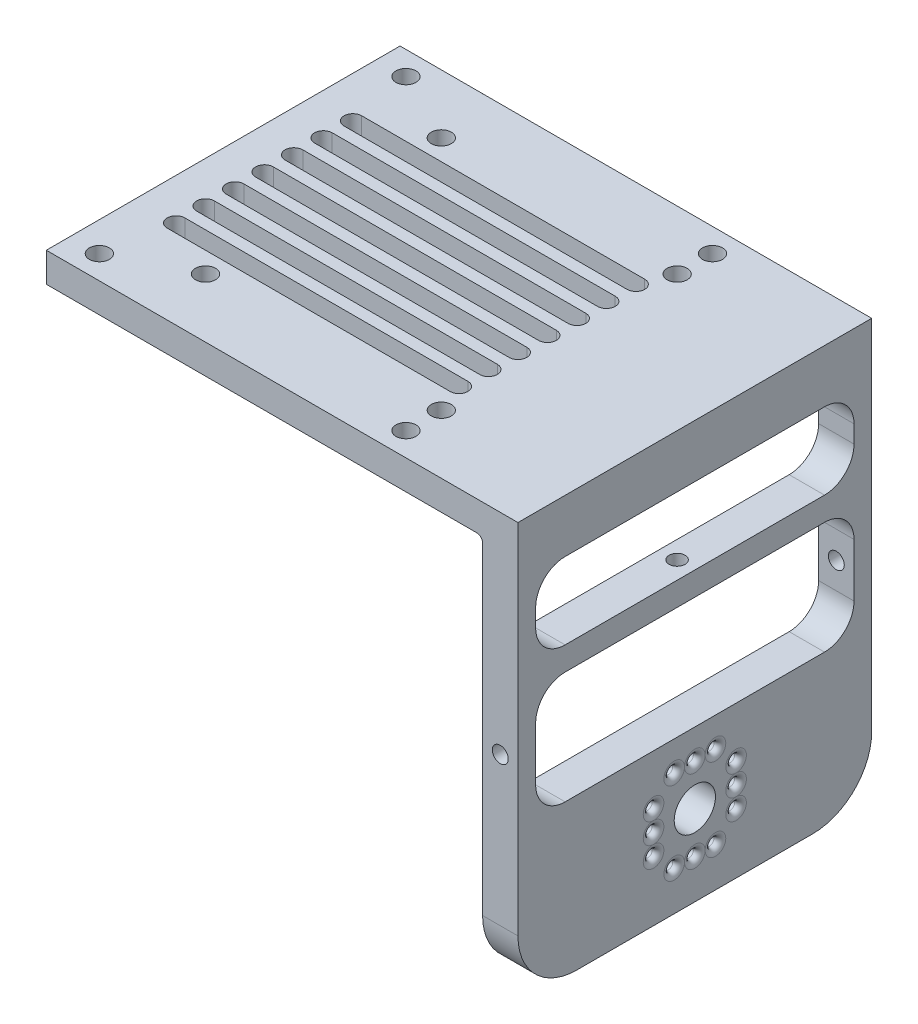
SolidWorks part; units mm, degrees
ref_plane "Front Plane" through (0, 0, 0) normal (0, 0, 1) x (1, 0, 0)
ref_plane "Top Plane" through (0, 0, 0) normal (0, 1, 0) x (1, 0, 0)
ref_plane "Right Plane" through (0, 0, 0) normal (1, 0, 0) x (0, 0, -1)
sketch "Sketch1" plane through (0, 0, 0) normal (0, 1, 0) x (1, 0, 0)
  line L0 (17, 50) -> (17, 10) construction
  line L1 (0, 0) -> (74, 0)
  line L2 (0, 0) -> (0, 60)
  line L3 (0, 60) -> (74, 60)
  line L4 (74, 0) -> (74, 60)
  line L5 (17, 10) -> (57, 10) construction
  line L6 (57, 10) -> (57, 50) construction
  line L7 (57, 50) -> (17, 50) construction
  line L8 (5, -3.2672) -> (5, 68.5158) construction
  line L9 (74, 30) -> (-36.7362, 30) construction
  line L10 (5, 56) -> (78.5335, 56) construction
  line L11 (5, 4) -> (68.1649, 4) construction
  circle A0 centre (17, 50) radius 1.7
  circle A1 centre (57, 50) radius 1.7
  circle A2 centre (57, 10) radius 1.7
  circle A3 centre (17, 10) radius 1.7
  circle A4 centre (5, 4) radius 1.7
  circle A5 centre (5, 56) radius 1.7
  circle A6 centre (57, 56) radius 1.7
  circle A7 centre (57, 4) radius 1.7
  dimension "D5" = 3.4
  dimension "D6" = 3.4
  dimension "D7" = 3.4
  dimension "D8" = 3.4
  dimension "D14" = 3.4
  dimension "D15" = 3.4
  dimension "D16" = 52
  dimension "D17" = 3.4
  dimension "D19" = 3.4
  dimension "D1" = 17
  dimension "D2" = 17
  dimension "D3" = 10
  dimension "D4" = 10
  dimension "D9" = 40
  dimension "D10" = 40
  dimension "D11" = 26
  dimension "D12" = 26
  dimension "D13" = 0
  dimension "D18" = 52
extrude "Boss-Extrude1" add sketch "Sketch1" along normal blind 5
sketch "Sketch2" plane through (0, 5, 0) normal (0, 1, 0) x (1, 0, 0)
  line L0 (0, 0) -> (74, 0) construction
  line L1 (74, 60) -> (80, 60)
  line L2 (74, 60) -> (74, 0)
  line L3 (74, 0) -> (80, 0)
  line L4 (80, 60) -> (80, 0)
  dimension "D1" = 6
  dimension "D2" = 0
extrude "Boss-Extrude2" add sketch "Sketch2" against normal blind 100
sketch "Sketch6" plane through (74, 0, 0) normal (-1, 0, 0) x (0, 0, 1)
  line L0 (-60, -95) -> (-60, 0) construction
  line L1 (2.3191, -65.7279) -> (-60, -65.7279)
  line L2 (2.3191, -65.7279) -> (2.3191, -97.9677)
  line L3 (2.3191, -97.9677) -> (-60, -97.9677)
  line L4 (-60, -65.7279) -> (-60, -97.9677)
  line L5 (2.3191, -65.7279) -> (-60, -97.9677) construction
  line L6 (2.3191, -97.9677) -> (-60, -65.7279) construction
  line L7 (-60, -95) -> (0, -95) construction
  line L8 (0, -95) -> (0, 0) construction
  point P0 (-28.8405, -81.8478)
  dimension "D1" = 2.9677
  dimension "D2" = 2.3191
  dimension "D3" = 29.2721
extrude "Cut-Extrude5" cut sketch "Sketch6" against normal blind 10
fillet "Fillet2" radius 10 2 edges at (77, -65.7279, 0) (77, -65.7279, -60)
sketch "Sketch9" plane through (74, 0, 0) normal (-1, 0, 0) x (0, 0, 1)
  line L0 (-30, 0) -> (-30, -65.7279) construction
  line L1 (0, 0) -> (-60, 0) construction
  line L2 (-10, -65.7279) -> (-50, -65.7279) construction
  line L3 (-30, -59.03) -> (-0.5609, -59.03) construction
  line L6 (-30, -59.03) -> (-59.4391, -59.03) construction
  circle A0 centre (-30, -59.03) radius 0.75
  circle A1 centre (-30, -52.03) radius 3.5
  arc A2 (-60, -55.7279) -> (-50, -65.7279) centre (-50, -55.7279) ccw construction
  circle A3 centre (-33.5, -59.03) radius 0.75
  circle A4 centre (-26.5, -59.03) radius 0.75
  arc A5 (-10, -65.7279) -> (0, -55.7279) centre (-10, -55.7279) ccw construction
  circle A6 centre (-37, -48.53) radius 0.75
  circle A7 centre (-37, -52.03) radius 0.75
  circle A8 centre (-37, -55.53) radius 0.75
  circle A9 centre (-26.5, -45.03) radius 0.75
  circle A10 centre (-30, -45.03) radius 0.75
  circle A11 centre (-33.5, -45.03) radius 0.75
  circle A12 centre (-23, -55.53) radius 0.75
  circle A13 centre (-23, -52.03) radius 0.75
  circle A14 centre (-23, -48.53) radius 0.75
  point P43 (-30, -52.03)
  dimension "D1" = 7
  dimension "D2" = 52.03
  dimension "D3" = 1.5
  dimension "D5" = 1.5
  dimension "D8" = 1.5
  dimension "D4" = 7
  dimension "D6" = 3.5
  dimension "D7" = 3.5
  dimension "D10" = 7
  dimension "D11" = 4.9497
  dimension "D9" = 4
extrude "Cut-Extrude7" cut sketch "Sketch9" against normal blind 10
sketch "Sketch10" plane through (74, 0, 0) normal (-1, 0, 0) x (0, 0, 1)
  line L0 (-52, -20.9721) -> (-8, -20.9721)
  line L1 (-3, -25.9721) -> (-3, -35.03)
  line L2 (-8, -40.03) -> (-52, -40.03)
  line L3 (-57, -35.03) -> (-57, -25.9721)
  line L4 (0, -55.7279) -> (0, 0) construction
  line L5 (-60, -55.7279) -> (-60, 0) construction
  arc A0 (-3, -35.03) -> (-8, -40.03) centre (-8, -35.03) cw
  arc A1 (-52, -40.03) -> (-57, -35.03) centre (-52, -35.03) cw
  arc A2 (-52, -20.9721) -> (-57, -25.9721) centre (-52, -25.9721) ccw
  arc A3 (-8, -20.9721) -> (-3, -25.9721) centre (-8, -25.9721) cw
  circle A4 centre (-30, -52.03) radius 3.5 construction
  dimension "D3" = 5
  dimension "D4" = 12
  dimension "D1" = 3
  dimension "D2" = 3
  dimension "D5" = 20.9721
extrude "Cut-Extrude8" cut sketch "Sketch10" against normal blind 10 contours L0 | L1 | L2 | L3 region at (74, -30.5011, -30)
fillet "Fillet3" radius 1 1 edges at (74, 0, -30)
sketch "Sketch11" plane through (0, 0, -60) normal (0, 0, -1) x (-1, 0, 0)
  line L0 (-80, -55.7279) -> (-80, 5) construction
  line L1 (-80, -55.7279) -> (-74, -55.7279) construction
  line L2 (-80, 5) -> (0, 5) construction
  line L3 (-69, 5) -> (-77, -30.57) construction
  circle A0 centre (-77, -30.57) radius 1.35
  dimension "D1" = 2.7
  dimension "D2" = 3
  dimension "D3" = 25.1579
extrude "Cut-Extrude9" cut sketch "Sketch11" against normal up to vertex (60 mm away) up to point (74, -1, 0)
sketch "Sketch13" plane through (0, -20.9721, 0) normal (0, -1, 0) x (1, 0, 0)
  line L0 (74, -30) -> (80, -30) construction
  line L1 (74, -52) -> (74, -8) construction
  line L2 (80, -8) -> (80, -52) construction
  circle A0 centre (77, -30) radius 1.35
  dimension "D1" = 2.7
extrude "Cut-Extrude11" cut sketch "Sketch13" against normal blind 10
sketch "Sketch15" plane through (74, 0, 0) normal (-1, 0, 0) x (0, 0, 1)
  line L4 (-3, -11.9721) -> (-3, -9)
  line L5 (-8, -4) -> (-52, -4)
  line L6 (-57, -9) -> (-57, -11.9721)
  line L7 (-52, -16.9721) -> (-8, -16.9721)
  line L8 (0, -55.7279) -> (0, -1) construction
  line L9 (-60, -55.7279) -> (-60, -1) construction
  line L10 (0, -1) -> (-60, -1) construction
  line L11 (-52, -20.9721) -> (-8, -20.9721) construction
  arc A2 (-57, -11.9721) -> (-52, -16.9721) centre (-52, -11.9721) ccw
  arc A3 (-52, -4) -> (-57, -9) centre (-52, -9) ccw
  arc A4 (-3, -9) -> (-8, -4) centre (-8, -9) ccw
  arc A5 (-3, -11.9721) -> (-8, -16.9721) centre (-8, -11.9721) cw
  point P11 (-30, -1)
  dimension "D5" = 5
  dimension "D1" = 3
  dimension "D2" = 3
  dimension "D3" = 3
  dimension "D4" = 4
extrude "Cut-Extrude12" cut sketch "Sketch15" against normal blind 10
sketch "Sketch16" plane through (0, 5, 0) normal (0, 1, 0) x (1, 0, 0)
  line L0 (7, 15) -> (55, 15) construction
  line L1 (7, 16.5) -> (55, 16.5)
  line L2 (7, 13.5) -> (55, 13.5)
  line L3 (7, 20) -> (55, 20) construction
  line L4 (7, 21.5) -> (55, 21.5)
  line L5 (7, 18.5) -> (55, 18.5)
  line L6 (7, 25) -> (55, 25) construction
  line L7 (7, 26.5) -> (55, 26.5)
  line L8 (7, 23.5) -> (55, 23.5)
  line L9 (7, 30) -> (55, 30) construction
  line L10 (7, 31.5) -> (55, 31.5)
  line L11 (7, 28.5) -> (55, 28.5)
  line L12 (7, 35) -> (55, 35) construction
  line L13 (7, 36.5) -> (55, 36.5)
  line L14 (7, 33.5) -> (55, 33.5)
  line L15 (7, 40) -> (55, 40) construction
  line L16 (7, 41.5) -> (55, 41.5)
  line L17 (7, 38.5) -> (55, 38.5)
  line L18 (7, 45) -> (55, 45) construction
  line L19 (7, 46.5) -> (55, 46.5)
  line L20 (7, 43.5) -> (55, 43.5)
  arc A0 (7, 16.5) -> (7, 13.5) centre (7, 15) ccw
  arc A1 (55, 13.5) -> (55, 16.5) centre (55, 15) ccw
  circle A2 centre (17, 10) radius 1.7 construction
  circle A3 centre (57, 10) radius 1.7 construction
  arc A4 (7, 21.5) -> (7, 18.5) centre (7, 20) ccw
  arc A5 (55, 18.5) -> (55, 21.5) centre (55, 20) ccw
  arc A6 (7, 26.5) -> (7, 23.5) centre (7, 25) ccw
  arc A7 (55, 23.5) -> (55, 26.5) centre (55, 25) ccw
  arc A8 (7, 31.5) -> (7, 28.5) centre (7, 30) ccw
  arc A9 (55, 28.5) -> (55, 31.5) centre (55, 30) ccw
  arc A10 (7, 36.5) -> (7, 33.5) centre (7, 35) ccw
  arc A11 (55, 33.5) -> (55, 36.5) centre (55, 35) ccw
  arc A12 (7, 41.5) -> (7, 38.5) centre (7, 40) ccw
  arc A13 (55, 38.5) -> (55, 41.5) centre (55, 40) ccw
  arc A14 (7, 46.5) -> (7, 43.5) centre (7, 45) ccw
  arc A15 (55, 43.5) -> (55, 46.5) centre (55, 45) ccw
  circle A16 centre (17, 50) radius 1.7 construction
  circle A17 centre (5, 4) radius 1.7 construction
  circle A18 centre (5, 56) radius 1.7 construction
  point P2 (31, 15)
  point P15 (31, 20)
  point P22 (31, 25)
  point P29 (31, 30)
  point P36 (31, 35)
  point P43 (31, 40)
  point P50 (31, 45)
  dimension "D3" = 2
  dimension "D6" = 5
  dimension "D1" = 5
  dimension "D2" = 3
  dimension "D4" = 2
  dimension "D7" = 2
  dimension "D5" = 7
extrude "Cut-Extrude13" cut sketch "Sketch16" against normal up to surface (5 mm away) up to face at (57, 0, -54.3)
fillet "Fillet4" radius 1 12 edges at (80, -59.03, -30.75) (80, -59.03, -34.25) (80, -55.53, -37.75) (80, -52.03, -37.75) (80, -48.53, -37.75) (80, -45.03, -34.25) (80, -45.03, -30.75) (80, -45.03, -27.25) (80, -48.53, -23.75) (80, -52.03, -23.75) (80, -55.53, -23.75) (80, -59.03, -27.25)
